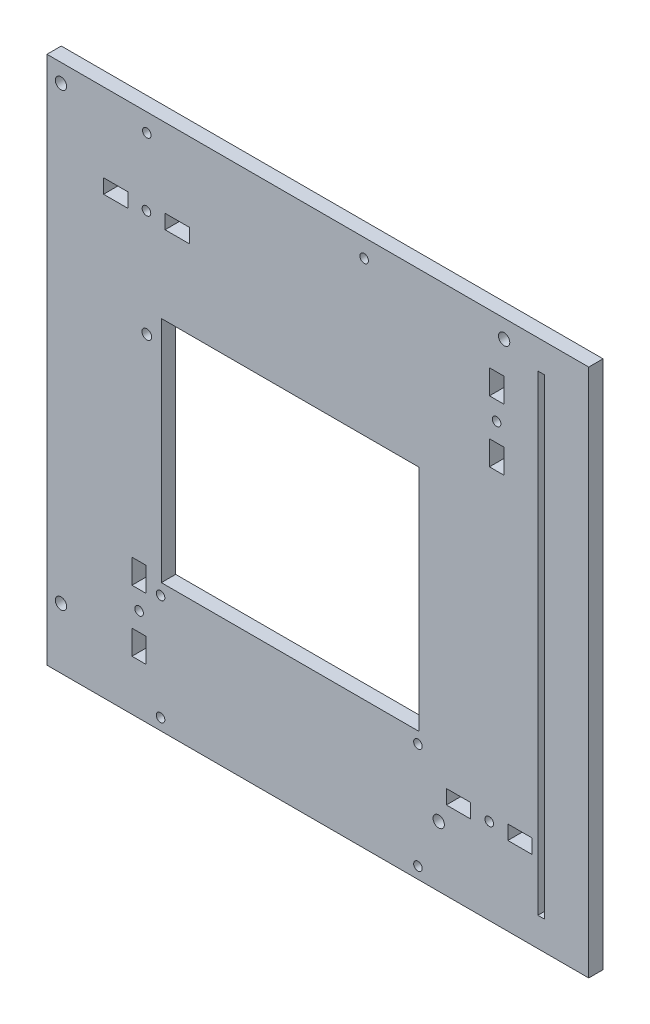
SolidWorks part; units mm, degrees
ref_plane "Front Plane" through (0, 0, 0) normal (0, 0, 1) x (1, 0, 0)
ref_plane "Top Plane" through (0, 0, 0) normal (0, 1, 0) x (1, 0, 0)
ref_plane "Right Plane" through (0, 0, 0) normal (1, 0, 0) x (0, 0, -1)
sketch "Sketch2" plane through (0, 0, 0) normal (0, 0, 1) x (1, 0, 0)
  line L0 (104.43, 85) -> (-85, -100) construction
  line L1 (-85, 85) -> (104.43, 85)
  line L2 (-85, 85) -> (-85, -100)
  line L3 (-85, -100) -> (104.43, -100)
  line L4 (104.43, 85) -> (104.43, -100)
  line L5 (96.43, 71.875) -> (96.43, 85) construction
  line L6 (88.43, -89.415) -> (87.11, -89.415) construction
  line L7 (96.43, -86.875) -> (96.43, -100) construction
  line L8 (88.43, 73.415) -> (88.43, -88.415) construction
  line L9 (87.11, -89.415) -> (87.11, 73.415) construction
  line L10 (88.43, 74.415) -> (87.11, 74.415) construction
  line L11 (-80.1, 78.65) -> (51.98, 78.65) construction
  line L12 (-80.1, 78.65) -> (-80.1, -78.83) construction
  line L13 (-80.1, -78.83) -> (51.98, -78.83) construction
  line L14 (51.98, 78.65) -> (51.98, -78.83) construction
  line L15 (74.84, 78.65) -> (-80.1, 78.65) construction
  line L16 (74.84, 78.65) -> (74.84, -78.83) construction
  line L17 (74.84, -78.83) -> (-80.1, -78.83) construction
  line L18 (-80.1, 78.65) -> (-80.1, -78.83) construction
  line L19 (88.93, -89.915) -> (86.61, -89.915)
  line L20 (88.93, -89.915) -> (88.93, 74.915)
  line L21 (88.93, 74.915) -> (86.61, 74.915)
  line L22 (86.61, -89.915) -> (86.61, 74.915)
  line L23 (88.93, -89.915) -> (86.61, 74.915) construction
  line L24 (88.93, 74.915) -> (86.61, -89.915) construction
  line L25 (-56.7109, 57.5) -> (-65.2109, 57.5)
  line L26 (25.9, 78.65) -> (-50.1, 78.65) construction
  line L27 (45, -55) -> (-45, -55)
  line L28 (45, -55) -> (45, 25)
  line L29 (45, 25) -> (-45, 25)
  line L30 (-45, -55) -> (-45, 25)
  line L31 (45, -55) -> (-45, 25) construction
  line L32 (45, 25) -> (-45, -55) construction
  line L33 (25.9, 78.65) -> (25.9, 17.65) construction
  line L34 (25.9, 17.65) -> (-50.1, 17.65) construction
  line L35 (-50.1, 78.65) -> (-50.1, 17.65) construction
  line L36 (-35.2109, 52.5) -> (-43.7109, 52.5)
  line L37 (-35.2109, 52.5) -> (-35.2109, 57.5)
  line L38 (-35.2109, 57.5) -> (-43.7109, 57.5)
  line L39 (-65.2109, 52.5) -> (-65.2109, 57.5)
  line L40 (-43.7109, 55) -> (-56.7109, 55) construction
  line L41 (-43.7109, 52.5) -> (-43.7109, 57.5)
  line L42 (74.715, 58.9259) -> (74.715, 67.4259)
  line L43 (-56.7109, 52.5) -> (-56.7109, 57.5)
  line L44 (-56.7109, 52.5) -> (-65.2109, 52.5)
  line L45 (69.715, 37.4259) -> (69.715, 45.9259)
  line L46 (69.715, 37.4259) -> (74.715, 37.4259)
  line L47 (74.715, 37.4259) -> (74.715, 45.9259)
  line L48 (69.715, 67.4259) -> (74.715, 67.4259)
  line L49 (69.715, 45.9259) -> (74.715, 45.9259)
  line L50 (69.715, 58.9259) -> (74.715, 58.9259)
  line L51 (69.715, 58.9259) -> (69.715, 67.4259)
  line L52 (72.215, 45.9259) -> (72.215, 58.9259) construction
  line L53 (76.1409, -72.5) -> (84.6409, -72.5)
  line L54 (54.6409, -67.5) -> (63.1409, -67.5)
  line L55 (54.6409, -67.5) -> (54.6409, -72.5)
  line L56 (54.6409, -72.5) -> (63.1409, -72.5)
  line L57 (84.6409, -67.5) -> (84.6409, -72.5)
  line L58 (63.1409, -67.5) -> (63.1409, -72.5)
  line L59 (76.1409, -67.5) -> (76.1409, -72.5)
  line L60 (76.1409, -67.5) -> (84.6409, -67.5)
  line L61 (63.1409, -70) -> (76.1409, -70) construction
  line L62 (-55.285, -73.9259) -> (-55.285, -82.4259)
  line L63 (-50.285, -52.4259) -> (-50.285, -60.9259)
  line L64 (-50.285, -52.4259) -> (-55.285, -52.4259)
  line L65 (-55.285, -52.4259) -> (-55.285, -60.9259)
  line L66 (-50.285, -82.4259) -> (-55.285, -82.4259)
  line L67 (-50.285, -60.9259) -> (-55.285, -60.9259)
  line L68 (-50.285, -73.9259) -> (-55.285, -73.9259)
  line L69 (-50.285, -73.9259) -> (-50.285, -82.4259)
  line L70 (-52.785, -60.9259) -> (-52.785, -73.9259) construction
  line L71 (74.715, 67.4259) -> (69.715, 67.4259) construction
  line L72 (69.715, 67.4259) -> (69.715, 58.9259) construction
  circle A0 centre (-80.1, 78.65) radius 1.98
  circle A1 centre (74.84, 78.65) radius 1.98
  circle A2 centre (51.98, -78.83) radius 1.98
  circle A3 centre (-80.1, -78.83) radius 1.98
  circle A4 centre (25.9, 78.65) radius 1.5
  circle A5 centre (-50.1, 78.65) radius 1.5
  circle A6 centre (-50.1, 17.65) radius 1.6948
  circle A7 centre (-50.2109, 55) radius 1.5
  circle A8 centre (72.215, 52.4259) radius 1.5
  circle A9 centre (69.6409, -70) radius 1.5
  circle A10 centre (-52.785, -67.4259) radius 1.5
  circle A11 centre (9.715, -7.5) radius 132.3903 construction
  point P8 (0, -15)
  point P28 (87.77, -7.5)
  dimension "D8" = 3
  dimension "D1" = 0.5
  dimension "D2" = 0.5
  dimension "D3" = 0.5
  dimension "D4" = 0.5
  dimension "D5" = 76
  dimension "D6" = 61
  dimension "D7" = 30
  dimension "D9" = 4
extrude "Boss-Extrude1" add sketch "Sketch2" along normal blind 5
sketch "Sketch3" plane through (0, 0, 5) normal (0, 0, 1) x (-1, 0, 0)
  line L1 (-44.715, 96) -> (45.285, 96) construction
  line L2 (-44.715, 96) -> (-44.715, 59) construction
  line L3 (-44.715, 59) -> (45.285, 59) construction
  line L4 (45.285, 96) -> (45.285, 59) construction
  line L5 (50.285, 82.4259) -> (50.285, 73.9259) construction
  line L6 (0, 55) -> (0, 100) construction
  line L7 (45, 55) -> (-45, 55) construction
  line L8 (85, 100) -> (-104.43, 100) construction
  line L9 (45.285, 77.5) -> (0, 77.5) construction
  circle A0 centre (45.285, 59) radius 1.5
  circle A1 centre (-44.715, 59) radius 1.5
  circle A2 centre (-44.715, 96) radius 1.5
  circle A3 centre (45.285, 96) radius 1.5
  dimension "D3" = 3
  dimension "D1" = 90
  dimension "D2" = 37
  dimension "D4" = 5
extrude "Cut-Extrude1" cut sketch "Sketch3" against normal blind 10
